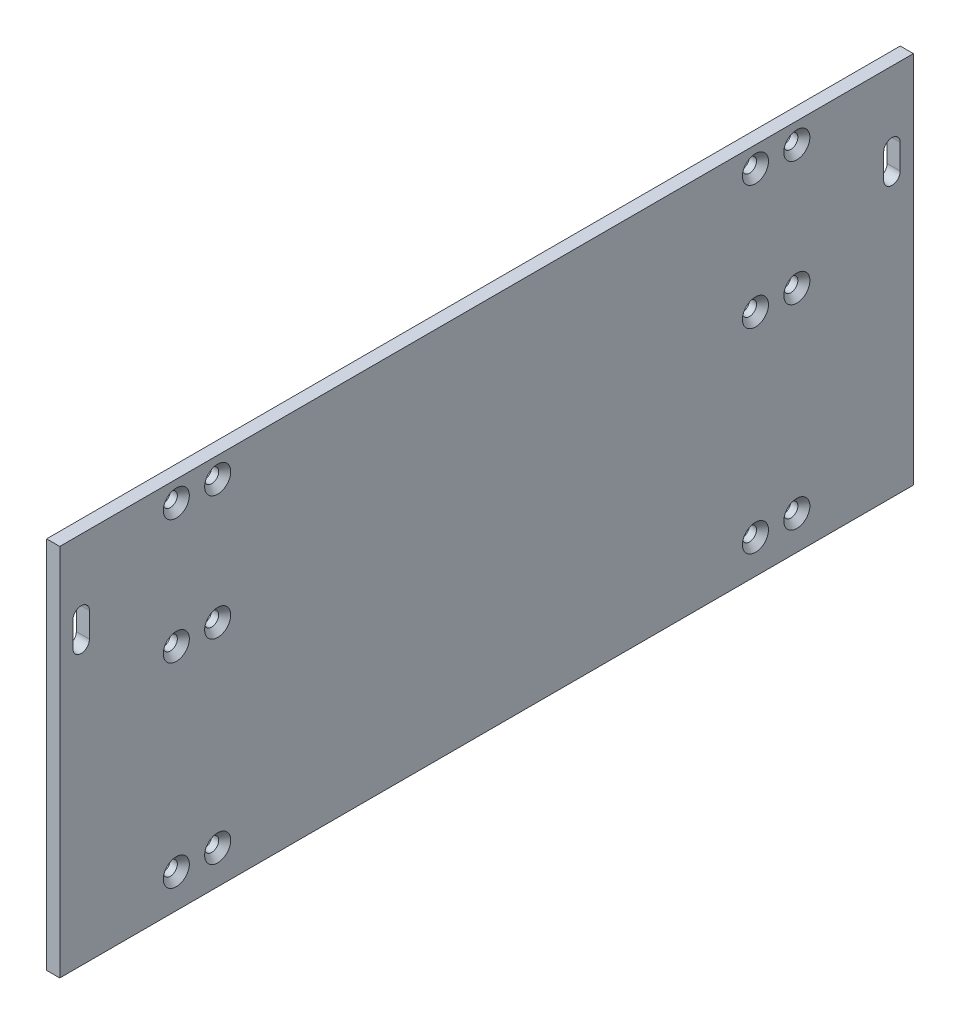
SolidWorks part; units mm, degrees
material "Garolite (G-10/FR4)"
ref_plane "Front Plane" through (0, 0, 0) normal (0, 0, 1) x (1, 0, 0)
ref_plane "Top Plane" through (0, 0, 0) normal (0, 1, 0) x (1, 0, 0)
ref_plane "Right Plane" through (0, 0, 0) normal (1, 0, 0) x (0, 0, -1)
sketch "Sketch1" plane through (0, 0, 0) normal (1, 0, 0) x (0, 0, -1)
  line L0 (103.175, 0) -> (103.175, 3.175)
  line L1 (-103.175, 0) -> (103.175, 0)
  line L2 (103.175, 3.175) -> (103.175, 47.175)
  line L3 (-103.175, 90.35) -> (103.175, 90.35)
  line L4 (-103.175, 3.175) -> (-103.175, 47.175)
  line L5 (-103.175, 3.175) -> (-103.175, 0)
  line L6 (103.175, 47.175) -> (103.175, 50.35)
  line L7 (103.175, 50.35) -> (103.175, 60.35)
  line L8 (103.175, 60.35) -> (103.175, 90.35)
  line L9 (-103.175, 47.175) -> (-103.175, 50.35)
  line L10 (-103.175, 50.35) -> (-103.175, 60.35)
  line L11 (-103.175, 60.35) -> (-103.175, 90.35)
  dimension "D1" = 206.35
  dimension "D2" = 30
  dimension "D3" = 3.175
  dimension "D4" = 44
  dimension "D5" = 3.175
  dimension "D6" = 10
extrude "Boss-Extrude1" add sketch "Sketch1" along normal blind 3.175
hole_wizard "CSK for M3 Flat Head Machine Screw1" positions "Sketch3" profile "Sketch2" countersink size "M3" standard "Ansi Metric" end condition through all
sketch "Sketch3" plane through (3.175, 0, 0) normal (1, 0, 0) x (0, 0, -1)
  line L0 (-65, 8.175) -> (-103.175, 8.175) construction
  line L1 (-103.175, 90.35) -> (-103.175, 0) construction
  line L3 (-103.175, 0) -> (103.175, 0) construction
  line L4 (-65, 55.35) -> (-103.175, 55.35) construction
  line L9 (-75, 55.35) -> (-75, 85.35) construction
  line L11 (-65, 55.35) -> (-65, 85.35) construction
  line L12 (-65, 85.35) -> (-75, 85.35) construction
  point P0 (-75, 8.175)
  point P1 (-65, 8.175)
  point P15 (-75, 55.35)
  point P17 (-65, 55.35)
  point P68 (-75, 85.35)
  point P70 (-65, 85.35)
  dimension "D1" = 8.175
  dimension "D2" = 28.175
  dimension "D3" = 10
  dimension "D4" = 30
  dimension "D5" = 28.175
  dimension "D6" = 10
  dimension "D8" = 55.35
sketch "Sketch2" plane through (3.175, 8.175, 75) normal (0, 1, 0) x (0, 0, -1)
  line L0 (0, 0) -> (0, 3.175)
  line L1 (0, 3.175) -> (1.7, 3.175)
  line L2 (1.7, 3.175) -> (1.7, 1.45)
  line L3 (1.7, 1.45) -> (3.15, 0)
  line L5 (3.15, 0) -> (0, 0)
  line L6 (-1.7, 1.45) -> (-3.15, 0) construction
  line L11 (0, -6.35) -> (0, 107.95) construction
  dimension "Thru Hole Dia." = 3.4
  dimension "Thru Hole Depth" = 3.175
  dimension "Near C'Sink Dia." = 6.3
  dimension "Near C'Sink Angle" = 90
mirror "Mirror1" about plane through (0, 0, 0) normal (0, 0, 1) of "CSK for M3 Flat Head Machine Screw1"
sketch "Sketch4" plane through (3.175, 0, 0) normal (1, 0, 0) x (0, 0, -1)
  line L0 (0, 0) -> (0, 90.35) construction
  line L1 (103.175, 90.35) -> (-103.175, 90.35) construction
  line L2 (-98, 73.35) -> (-98, 67.35) construction
  line L3 (-96, 73.35) -> (-96, 67.35)
  line L4 (-100, 73.35) -> (-100, 67.35)
  line L6 (98, 73.35) -> (98, 67.35) construction
  line L7 (96, 73.35) -> (96, 67.35)
  line L8 (100, 73.35) -> (100, 67.35)
  line L9 (-103.175, 90.35) -> (-103.175, 0) construction
  arc A0 (-96, 73.35) -> (-100, 73.35) centre (-98, 73.35) ccw
  arc A1 (-100, 67.35) -> (-96, 67.35) centre (-98, 67.35) ccw
  arc A2 (96, 73.35) -> (100, 73.35) centre (98, 73.35) cw
  arc A3 (100, 67.35) -> (96, 67.35) centre (98, 67.35) cw
  point P7 (-98, 70.35)
  point P16 (98, 70.35)
  dimension "D3" = 2
  dimension "D1" = 3.175
  dimension "D2" = 6
  dimension "D4" = 20
extrude "Cut-Extrude1" cut sketch "Sketch4" against normal through all
